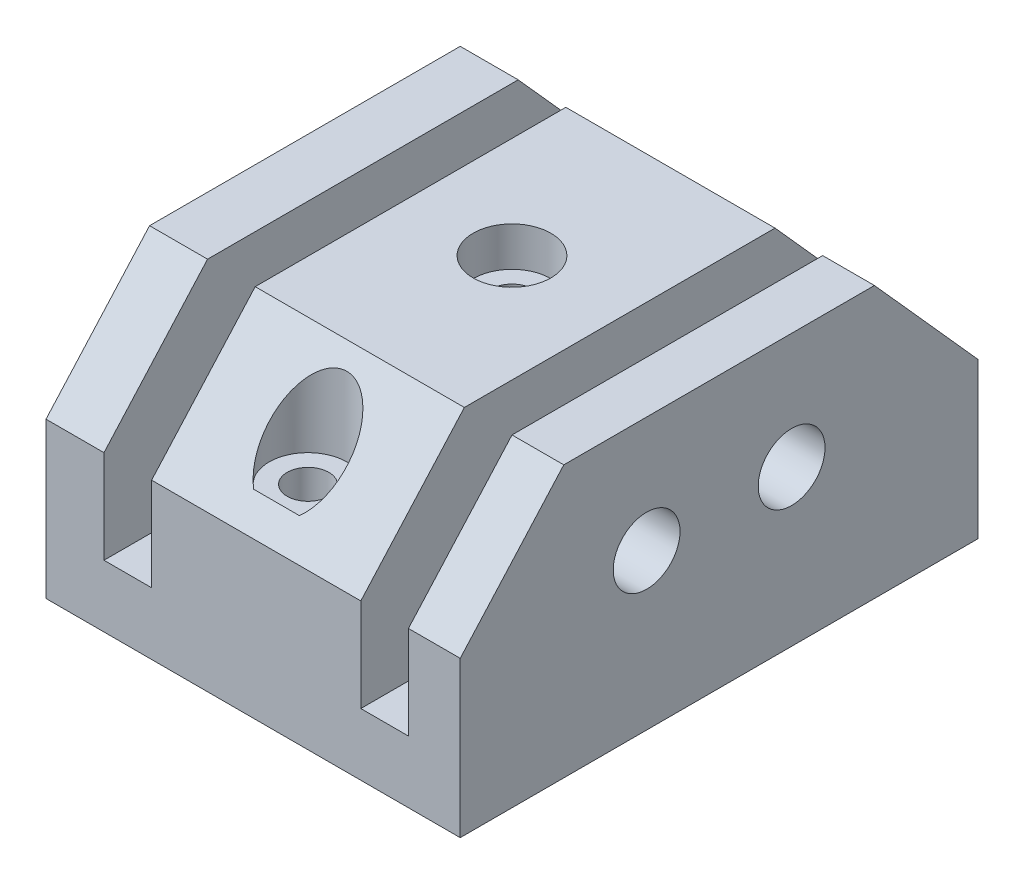
SolidWorks part; units mm, degrees
ref_plane "Front Plane" through (0, 0, 0) normal (0, 0, 1) x (1, 0, 0)
ref_plane "Top Plane" through (0, 0, 0) normal (0, 1, 0) x (1, 0, 0)
ref_plane "Right Plane" through (0, 0, 0) normal (1, 0, 0) x (0, 0, -1)
sketch "Sketch1" plane through (0, 0, 0) normal (1, 0, 0) x (0, 0, -1)
  line L1 (0, 0) -> (63.5, 0)
  line L2 (0, 0) -> (0, 6.35)
  line L3 (0, 6.35) -> (63.5, 6.35)
  line L4 (63.5, 0) -> (63.5, 6.35)
  dimension "D1" = 6.35
  dimension "D2" = 63.5
extrude "Boss-Extrude1" add sketch "Sketch1" against normal blind 50.8
sketch "Sketch2" plane through (0, 0, 0) normal (1, 0, 0) x (0, 0, -1)
  line L0 (0, 6.35) -> (0, 19.05)
  line L1 (0, 19.05) -> (12.7, 33.249)
  line L2 (12.7, 33.249) -> (50.8, 33.249)
  line L3 (50.8, 33.249) -> (63.5, 19.05)
  line L4 (63.5, 19.05) -> (63.5, 6.35)
  line L5 (63.5, 6.35) -> (0, 6.35)
  point P7 (31.75, 33.249)
  point P10 (31.75, 6.35)
  dimension "D1" = 38.1
  dimension "D2" = 12.7
  dimension "D3" = 12.7
  dimension "D4" = 19.05
  dimension "D5" = 19.05
extrude "Boss-Extrude2" add sketch "Sketch2" against normal blind 50.8
sketch "Sketch10" plane through (0, 0, -63.5) normal (0, 0, -1) x (-1, 0, 0)
  line L1 (50.8, 33.249) -> (0, 33.249) construction
  line L3 (6.35, 7.62) -> (6.35, 33.249)
  line L4 (6.35, 33.249) -> (12.192, 33.249)
  line L5 (12.192, 7.62) -> (12.192, 33.249)
  line L6 (6.35, 7.62) -> (12.192, 7.62)
  line L8 (50.8, 0) -> (0, 0) construction
  point P11 (12.192, 7.62)
  dimension "D1" = 7.62
  dimension "D2" = 5.842
  dimension "D3" = 6.35
extrude "Cut-Extrude1" cut sketch "Sketch10" against normal through all
pattern_linear "LPattern3" count 2 spacing 31.496 along (-1, 0, 0) of "Cut-Extrude1"
sketch "Sketch11" plane through (0, 0, 0) normal (1, 0, 0) x (0, 0, -1)
  circle A0 centre (22.86, 19.05) radius 4.0957
  circle A1 centre (22.86, 19.05) radius 7.9375 construction
  circle A2 centre (40.64, 19.05) radius 4.0958
  circle A3 centre (40.64, 19.05) radius 7.9375 construction
  dimension "D1" = 8.1915
  dimension "D3" = 15.875
  dimension "D4" = 8.1915
  dimension "D6" = 15.875
  dimension "D2" = 10.16
  dimension "D5" = 10.16
extrude "Cut-Extrude2" cut sketch "Sketch11" against normal through all
sketch "Sketch14" plane through (0, 33.249, 0) normal (0, 1, 0) x (1, 0, 0)
  line L3 (-37.846, 12.7) -> (-37.846, 50.8) construction
  point P0 (-25.4, 31.75)
  point P4 (-37.846, 31.75)
  dimension "D1" = 12.446
hole_wizard "CBORE for #10 Socket Head Cap Screw1" positions "Sketch15" profile "Sketch16" counterbore size "#10" standard "ANSI Inch" end condition up to next
sketch "Sketch15" plane through (0, 33.249, 0) normal (0, 1, 0) x (1, 0, 0)
  point P0 (-25.4, 31.75)
sketch "Sketch16" plane through (-25.4, 33.249, -31.75) normal (1, 0, 0) x (0, 0, 1)
  line L0 (0, 0) -> (0, 33.249)
  line L1 (0, 33.249) -> (2.5527, 33.249)
  line L3 (2.5527, 33.249) -> (2.5527, 4.826)
  line L4 (2.5527, 4.826) -> (4.7625, 4.826)
  line L5 (4.7625, 4.826) -> (4.7625, 0)
  line L7 (4.7625, 0) -> (0, 0)
  line L11 (0, -6.35) -> (0, 107.95) construction
  dimension "Thru Hole Dia." = 5.1054
  dimension "Thru Hole Depth" = 33.249
  dimension "C'Bore Dia." = 9.525
  dimension "C'Bore Depth" = 4.826
sketch "Sketch17" plane through (0, 40.0201, -44.7438) normal (0, 0.6667, -0.7454) x (-1, 0, 0)
  line L0 (12.192, -28.1343) -> (12.192, -9.0843) construction
  line L1 (37.846, -9.0843) -> (12.192, -9.0843) construction
  point P0 (25.019, -18.6093)
  point P4 (12.192, -18.6093)
  point P7 (25.019, -9.0843)
sketch "Sketch18" plane through (0, 8.4667, 9.466) normal (0, 0.6667, 0.7454) x (1, 0, 0)
  line L0 (-12.192, 33.249) -> (-12.192, 14.199) construction
  line L1 (-37.846, 33.249) -> (-12.192, 33.249) construction
  point P0 (-25.019, 23.724)
  point P1 (-25.019, 23.724)
  point P4 (-12.192, 23.724)
  point P7 (-25.019, 33.249)
ref_plane "Plane2" through (0, 33.02, 0) normal (0, -1, 0) x (-1, 0, 0)
hole_wizard "CBORE for #10 Socket Head Cap Screw3" positions "Sketch24" profile "Sketch25" counterbore size "#10" standard "ANSI Inch" end condition up to next
sketch "Sketch24" plane through (0, 33.02, 0) normal (0, -1, 0) x (-1, 0, 0)
  point P0 (25.019, 6.35)
  point P2 (25.019, 57.15)
sketch "Sketch25" plane through (-25.019, 33.02, -6.35) normal (1, 0, 0) x (0, 0, 1)
  line L0 (0, 0) -> (0, 33.02)
  line L1 (0, 33.02) -> (2.5527, 33.02)
  line L3 (2.5527, 33.02) -> (2.5527, 11.176)
  line L4 (2.5527, 11.176) -> (4.7625, 11.176)
  line L5 (4.7625, 11.176) -> (4.7625, 0)
  line L7 (4.7625, 0) -> (0, 0)
  line L11 (0, -6.35) -> (0, 107.95) construction
  dimension "Thru Hole Dia." = 5.1054
  dimension "Thru Hole Depth" = 33.02
  dimension "C'Bore Dia." = 9.525
  dimension "C'Bore Depth" = 11.176
ref_plane "midplane" through (0, 0, -31.75) normal (0, 0, -1) x (-1, 0, 0)
